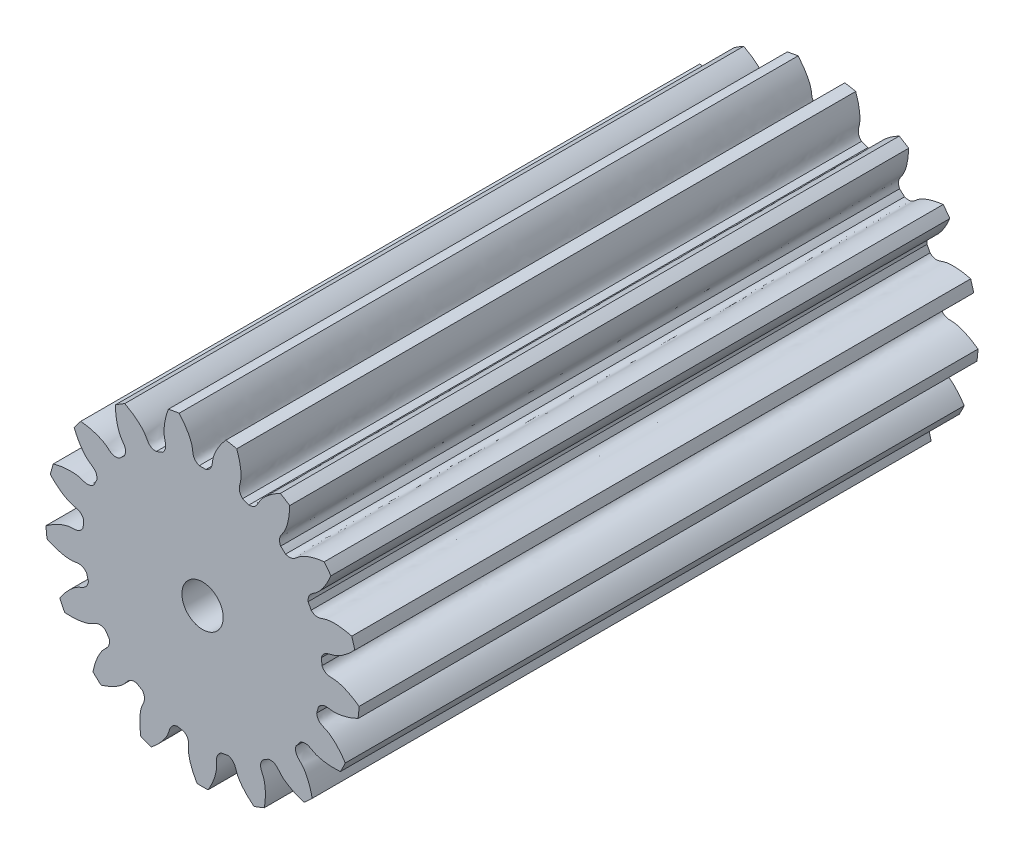
SolidWorks part; units mm, degrees
ref_plane "前视基准面" through (0, 0, 0) normal (0, 0, 1) x (1, 0, 0)
ref_plane "上视基准面" through (0, 0, 0) normal (0, 1, 0) x (1, 0, 0)
ref_plane "右视基准面" through (0, 0, 0) normal (1, 0, 0) x (0, 0, -1)
sketch "草图1" plane through (0, 0, 0) normal (0, 0, 1) x (1, 0, 0)
  circle A0 centre (0, 0) radius 7.6
extrude "凸台-拉伸1" add sketch "草图1" along normal blind 30
ref_axis "基准轴1" through (0, 0, -5.3001) along (0, 0, 1)
sketch "草图2" plane through (0, 0, 0) normal (0, 0, 1) x (1, 0, 0)
  line L0 (0, 0) -> (0, 7.6) construction
  circle A0 centre (0, 0) radius 7.6 construction
  arc A1 (0.1614, 5.7978) -> (-0.1614, 5.7978) centre (0, 0) ccw
  arc A2 (2.4925, 8.5926) -> (-2.4925, 8.5926) centre (0, 0) ccw
  spline S0 degree 3 poles (0.1614, 5.7978) (0.5023, 5.9399) (0.453, 6.2039) (0.5106, 6.4519) (0.516, 6.4729) (0.5224, 6.4963) (0.53, 6.5221) (0.539, 6.5501) (0.5492, 6.5803) (0.561, 6.6128) (0.5743, 6.6473) (0.5893, 6.684) (0.6061, 6.7227) (0.6246, 6.7634) (0.6451, 6.8061) (0.6676, 6.8505) (0.6921, 6.8968) (0.7189, 6.9449) (0.7478, 6.9945) (0.7791, 7.0458) (0.8128, 7.0986) (0.849, 7.1529) (0.8876, 7.2085) (0.9289, 7.2653) (0.9729, 7.3234) (1.0196, 7.3826) (1.0691, 7.4429) (1.1214, 7.5041) (1.1767, 7.5661) (1.2349, 7.6289) (1.2962, 7.6923) (1.3605, 7.7563) (1.4279, 7.8208) (1.4985, 7.8856) (1.5723, 7.9508) (1.6493, 8.016) (1.7296, 8.0814) (1.8132, 8.1467) (1.9001, 8.2118) (1.9904, 8.2767) (2.0841, 8.3412) (2.1812, 8.4052) (2.3167, 8.4907) (2.4213, 8.5524) (2.4925, 8.5926) knots 0 0 0 0 0.193883 0.199024 0.204851 0.211363 0.21856 0.226443 0.235011 0.244265 0.254205 0.264829 0.27614 0.288136 0.300817 0.314184 0.328236 0.342973 0.358397 0.374505 0.391299 0.408779 0.426944 0.445795 0.465331 0.485552 0.506459 0.528051 0.550329 0.573293 0.596941 0.621276 0.646296 0.672001 0.698392 0.725468 0.753229 0.781677 0.810809 0.840627 0.871131 0.90232 0.934195 1 1 1 1
  spline S1 degree 3 poles (-0.1614, 5.7978) (-0.5023, 5.9399) (-0.453, 6.2039) (-0.5106, 6.4519) (-0.516, 6.4729) (-0.5224, 6.4963) (-0.53, 6.5221) (-0.539, 6.5501) (-0.5492, 6.5803) (-0.561, 6.6128) (-0.5743, 6.6473) (-0.5893, 6.684) (-0.6061, 6.7227) (-0.6246, 6.7634) (-0.6451, 6.8061) (-0.6676, 6.8505) (-0.6921, 6.8968) (-0.7189, 6.9449) (-0.7478, 6.9945) (-0.7791, 7.0458) (-0.8128, 7.0986) (-0.849, 7.1529) (-0.8876, 7.2085) (-0.9289, 7.2653) (-0.9729, 7.3234) (-1.0196, 7.3826) (-1.0691, 7.4429) (-1.1214, 7.5041) (-1.1767, 7.5661) (-1.2349, 7.6289) (-1.2962, 7.6923) (-1.3605, 7.7563) (-1.4279, 7.8208) (-1.4985, 7.8856) (-1.5723, 7.9508) (-1.6493, 8.016) (-1.7296, 8.0814) (-1.8132, 8.1467) (-1.9001, 8.2118) (-1.9904, 8.2767) (-2.0841, 8.3412) (-2.1812, 8.4052) (-2.3167, 8.4907) (-2.4213, 8.5524) (-2.4925, 8.5926) knots 0 0 0 0 0.193883 0.199024 0.204851 0.211363 0.21856 0.226443 0.235011 0.244265 0.254205 0.264829 0.27614 0.288136 0.300817 0.314184 0.328236 0.342973 0.358397 0.374505 0.391299 0.408779 0.426944 0.445795 0.465331 0.485552 0.506459 0.528051 0.550329 0.573293 0.596941 0.621276 0.646296 0.672001 0.698392 0.725468 0.753229 0.781677 0.810809 0.840627 0.871131 0.90232 0.934195 1 1 1 1
extrude "切除-拉伸1" cut sketch "草图2" along normal through all
pattern_circular "阵列(圆周)1" count 17 every 21.176 about axis through (0, 0, -5.3001) along (0, 0, 1) of "切除-拉伸1"
sketch "草图3" plane through (0, 0, 0) normal (0, 0, 1) x (1, 0, 0)
  circle A0 centre (0, 0) radius 6.8 construction
  dimension "Dn" = 13.6
sketch "草图5" plane through (0, 0, 0) normal (0, 0, -1) x (-1, 0, 0)
  circle A0 centre (0, 0) radius 1
  dimension "D1" = 2
extrude "切除-拉伸2" cut sketch "草图5" against normal through all
ref_axis "基准轴2" through (0, 0, 45.4288) along (0, 0, -1)
